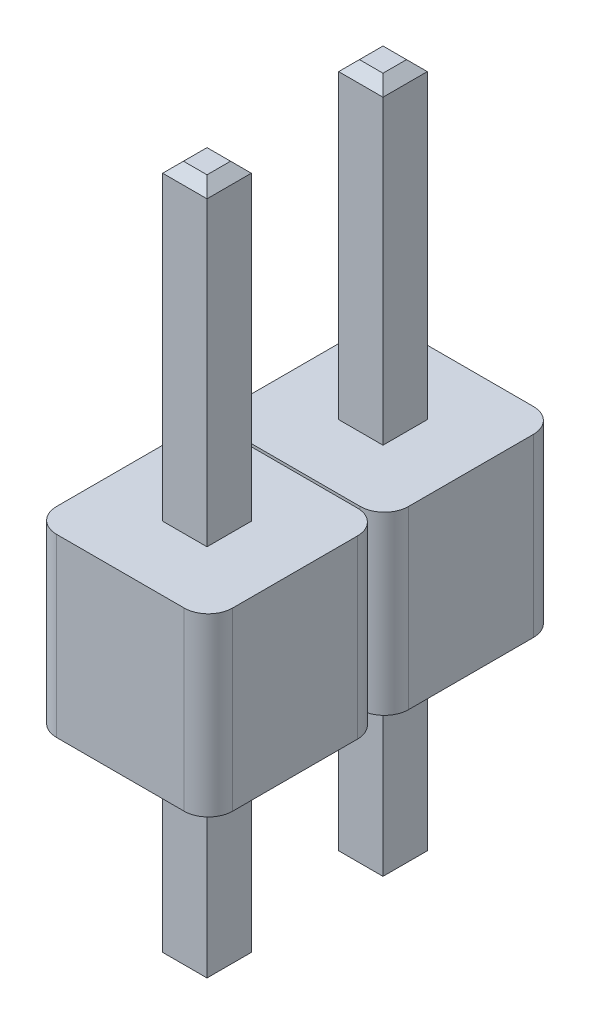
SolidWorks part; units mm, degrees
ref_plane "Front Plane" through (0, 0, 0) normal (0, 0, 1) x (1, 0, 0)
ref_plane "Top Plane" through (0, 0, 0) normal (0, 1, 0) x (1, 0, 0)
ref_plane "Right Plane" through (0, 0, 0) normal (1, 0, 0) x (0, 0, -1)
sketch "Sketch1" plane through (0, 0, 0) normal (0, 1, 0) x (1, 0, 0)
  line L1 (0, 0) -> (0.64, 0)
  line L2 (0, 0) -> (0, 0.64)
  line L3 (0, 0.64) -> (0.64, 0.64)
  line L4 (0.64, 0) -> (0.64, 0.64)
  dimension "D1" = 0.64
  dimension "D2" = 0.64
extrude "Boss-Extrude1" add sketch "Sketch1" along normal blind 10.04
chamfer "Chamfer1" distance 0.15 angle 45 8 edges at (0.32, 0, 0) (0.64, 0, -0.32) (0.32, 0, -0.64) (0, 0, -0.32) (0.32, 10.04, -0.64) (0.64, 10.04, -0.32) (0.32, 10.04, 0) (0, 10.04, -0.32)
ref_plane "Plane1" through (0, 5.54, 0) normal (0, 1, 0) x (1, 0, 0)
sketch "Sketch3" plane through (0, 5.54, 0) normal (0, 1, 0) x (1, 0, 0)
  line L0 (0.32, 0.64) -> (0.32, 0) construction
  line L1 (0, 0.64) -> (0.64, 0.64) construction
  line L2 (0.64, 0) -> (0, 0) construction
  line L4 (-0.6, -0.93) -> (1.24, -0.93)
  line L5 (-0.95, -0.58) -> (-0.95, 1.22)
  line L6 (-0.6, 1.57) -> (1.24, 1.57)
  line L7 (1.59, -0.58) -> (1.59, 1.22)
  line L8 (-0.95, -0.93) -> (1.59, 1.57) construction
  line L9 (-0.95, 1.57) -> (1.59, -0.93) construction
  arc A0 (-0.6, -0.93) -> (-0.95, -0.58) centre (-0.6, -0.58) cw
  arc A1 (1.24, 1.57) -> (1.59, 1.22) centre (1.24, 1.22) cw
  arc A2 (-0.95, 1.22) -> (-0.6, 1.57) centre (-0.6, 1.22) cw
  arc A3 (1.24, -0.93) -> (1.59, -0.58) centre (1.24, -0.58) ccw
  point P6 (0.32, 0.32)
  point P7 (0.32, 0.32)
  dimension "D3" = 0.35
  dimension "D1" = 2.5
  dimension "D2" = 2.54
extrude "Boss-Extrude2" add sketch "Sketch3" against normal blind 2.54
ref_axis "Axis1" through (0.32, 3, 0.93) along (0, 0, -1)
pattern_linear "LPattern2" count 2 spacing 2.54 along (0, 0, -1) of bodies 102
